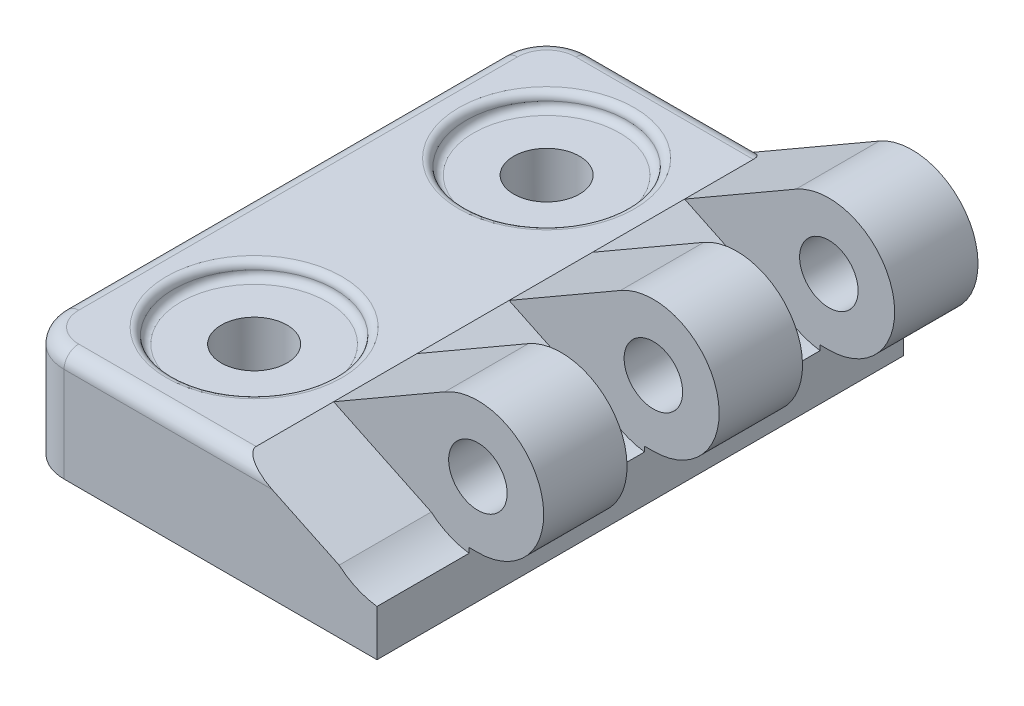
SolidWorks part; units mm, degrees
ref_plane "Front Plane" through (0, 0, 0) normal (0, 0, 1) x (1, 0, 0)
ref_plane "Top Plane" through (0, 0, 0) normal (0, 1, 0) x (1, 0, 0)
ref_plane "Right Plane" through (0, 0, 0) normal (1, 0, 0) x (0, 0, -1)
sketch "Croquis1" plane through (0, 0, 0) normal (0, 0, 1) x (1, 0, 0)
  line L0 (12.75, 7.8971) -> (5.134, 3.5)
  line L1 (-10, -4) -> (14.4, -4)
  line L2 (-10, -4) -> (-10, 3.5)
  line L3 (-10, 3.5) -> (5.134, 3.5)
  line L4 (15, -0.5) -> (14.4, -0.5)
  line L5 (-10, -4) -> (15, 4) construction
  line L6 (-10, 3.5) -> (18.6783, -4.5299) construction
  line L8 (14.4, -0.5) -> (14.4, -4)
  arc A0 (15, -0.5) -> (12.75, 7.8971) centre (15, 4) ccw
  circle A1 centre (15, 4) radius 1.5
  point P0 (2.5, 0)
  dimension "D3" = 3
  dimension "D4" = 4.5
  dimension "D1" = 7.5
  dimension "D2" = 25
  dimension "D5" = 30
  dimension "D6" = 0.6
  dimension "D7" = 3.5
extrude "Saliente-Extruir1" add sketch "Croquis1" against normal blind 36
sketch "Croquis2" plane through (0, 0, 0) normal (0, 0, 1) x (1, 0, 0)
  line L1 (14.4, -0.8426) -> (15, -0.5)
  line L2 (5.134, 3.5) -> (11.8076, 0.3095)
  line L3 (14.4, -4) -> (14.4, -0.5) construction
  line L5 (12.75, 7.8971) -> (5.134, 3.5) construction
  line L7 (12.75, 7.8971) -> (5.134, 3.5)
  arc A0 (15, -0.5) -> (12.75, 7.8971) centre (15, 4) ccw construction
  arc A1 (14.4, -0.8426) -> (11.8076, 0.3095) centre (15, 4) cw
  arc A2 (15, -0.5) -> (12.75, 7.8971) centre (15, 4) ccw
extrude "Cortar-Extruir1" cut sketch "Croquis2" against normal blind 6.3
pattern_linear "MatrizL1" count 3 spacing 12 along (0, 0, -1) of "Cortar-Extruir1"
sketch "Croquis3" plane through (0, 3.5, 0) normal (0, 1, 0) x (1, 0, 0)
  line L0 (-2, 28) -> (-2, 8) construction
  line L1 (5.134, 36) -> (-10, 36) construction
  line L2 (-10, 36) -> (-10, 0) construction
  circle A0 centre (-2, 28) radius 2.25
  circle A1 centre (-2, 8) radius 2.25
  dimension "D1" = 4.5
  dimension "D2" = 4.5
  dimension "D3" = 20
  dimension "D4" = 8
  dimension "D5" = 8
extrude "Cortar-Extruir2" cut sketch "Croquis3" against normal through all
fillet "Redondeo1" radius 3 2 edges at (-10, -0.25, 0) (-10, -0.25, -36)
fillet "Redondeo2" radius 1 5 edges at (-0.933, 3.5, -36) (-9.1213, 3.5, -35.1213) (-0.933, 3.5, 0) (-9.1213, 3.5, -0.8787) (-10, 3.5, -18)
sketch "Esquisse1" plane through (0, 3.5, 0) normal (0, 1, 0) x (1, 0, 0)
  circle A0 centre (-2, 28) radius 5.5
  circle A1 centre (-2, 8) radius 5.5
  dimension "D1" = 11
  dimension "D2" = 11
extrude "Enlèv. mat.-Extru.1" cut sketch "Esquisse1" against normal blind 1
fillet "Congé1" radius 0.5 4 edges at (-7.5, 3.5, -8) (-7.5, 2.5, -8) (-7.5, 3.5, -28) (-7.5, 2.5, -28)
sketch "Esquisse2" plane through (0, 0, -6.3) normal (0, 0, 1) x (1, 0, 0)
  circle A0 centre (15, 4) radius 2
  dimension "D1" = 4
extrude "Enlèv. mat.-Extru.2" cut sketch "Esquisse2" against normal blind 30
equation "\"num_dents\"= 3"
equation "\"gap\"= .6"
equation "\"llarg\"= 36"
equation "\"D1@Saliente-Extruir1\"=\"llarg\""
equation "\"D1@Cortar-Extruir1\"=(\"llarg\"-\"num_dents\"*\"gap\")/(2*\"num_dents\")+\"gap\""
equation "\"D1@MatrizL1\"=\"num_dents\""
equation "\"D3@MatrizL1\"=\"llarg\"/\"num_dents\""
equation "\"D2@Croquis3\"=\"D1@Croquis3\""
equation "\"D4@Croquis3\"=(\"llarg\"-\"D3@Croquis3\")/2"
equation "\"D5@Croquis3\"=\"D4@Croquis3\""
